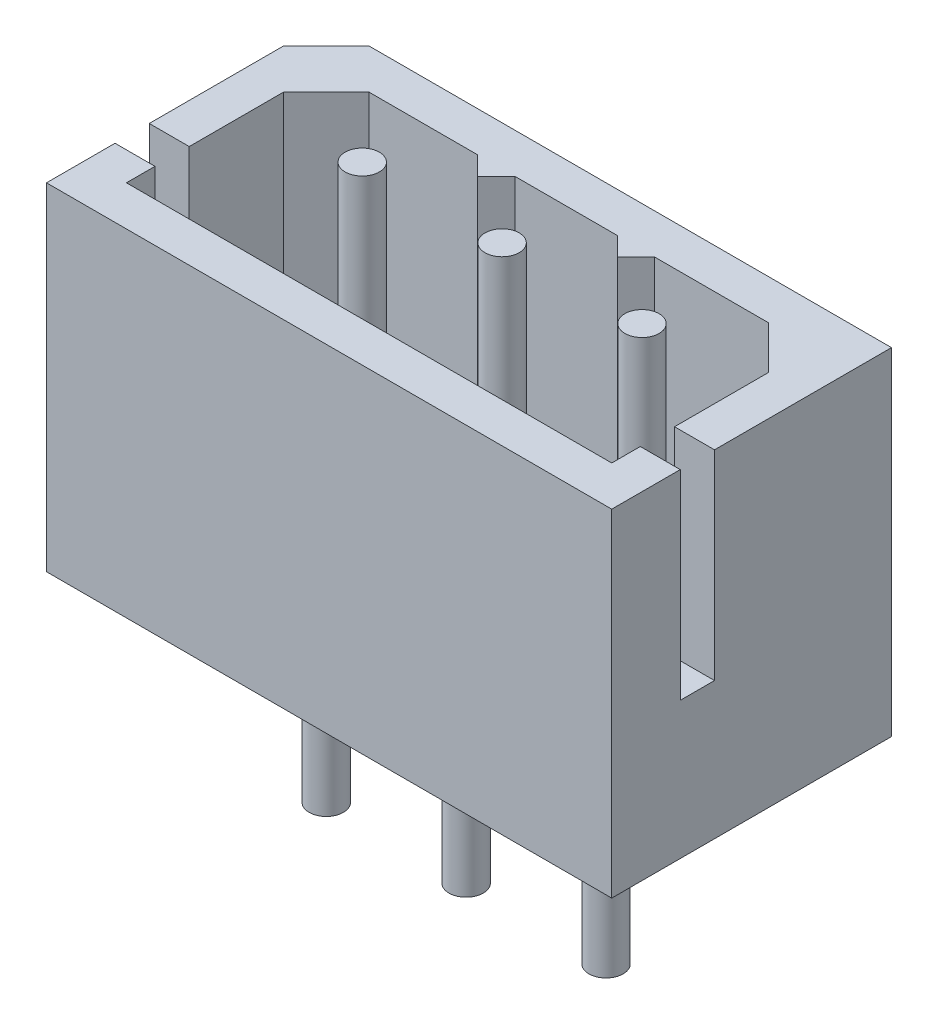
SolidWorks part; units mm, degrees
ref_plane "Front Plane" through (0, 0, 0) normal (0, 0, 1) x (1, 0, 0)
ref_plane "Top Plane" through (0, 0, 0) normal (0, 1, 0) x (1, 0, 0)
ref_plane "Right Plane" through (0, 0, 0) normal (1, 0, 0) x (0, 0, -1)
sketch "Sketch1" plane through (0, 0, 0) normal (0, 1, 0) x (1, 0, 0)
  line L0 (-4.2, 2.45) -> (-4.95, 1.7)
  line L1 (-4.2, 2.45) -> (4.95, 2.45)
  line L2 (-4.95, 1.7) -> (-4.95, -2.45)
  line L3 (-4.95, -2.45) -> (4.95, -2.45)
  line L4 (4.95, 2.45) -> (4.95, -2.45)
  line L5 (-4.95, 2.45) -> (4.95, -2.45) construction
  line L6 (-4.95, -2.45) -> (4.95, 2.45) construction
  point P0 (0, 0)
  dimension "D1" = 4.9
  dimension "D2" = 9.9
extrude "Boss-Extrude1" add sketch "Sketch1" against normal blind 5.9
sketch "Sketch2" plane through (0, -5.9, 0) normal (0, -1, 0) x (1, 0, 0)
  line L0 (-4.95, 0) -> (4.95, 0) construction
  line L1 (-4.95, -1.7) -> (-4.95, 2.45) construction
  line L2 (4.95, 2.45) -> (4.95, -2.45) construction
  line L3 (0, 2.45) -> (0, -2.45) construction
  line L4 (-4.95, 2.45) -> (4.95, 2.45) construction
  line L5 (4.95, -2.45) -> (-4.2, -2.45) construction
  line L6 (-2.5, 0) -> (-0.05, 0) construction
  line L7 (-4.95, -1.7) -> (-4.95, 2.45) construction
  line L8 (4.95, -2.45) -> (-4.2, -2.45) construction
  circle A0 centre (-2.5, 0) radius 0.3
  circle A1 centre (-0.05, 0) radius 0.3
  circle A2 centre (2.4, 0) radius 0.3
  dimension "D1" = 0.6
  dimension "D2" = 2.45
  dimension "D5" = 2.45
  dimension "D4" = 2.45
  dimension "D3" = 3
extrude "Boss-Extrude2" add sketch "Sketch2" along normal blind 3.5
sketch "Sketch3" plane through (0, 0, 0) normal (0, 1, 0) x (1, 0, 0)
  line L0 (-4.95, -2.45) -> (4.95, -2.45) construction
  line L1 (-3.5, 1.75) -> (3.5, 1.75)
  line L2 (-4.25, 1) -> (-4.25, -0.65)
  line L3 (-4.25, -1.75) -> (4.25, -1.75)
  line L4 (4.25, 1) -> (4.25, -0.65)
  line L5 (-4.25, 1.75) -> (4.25, -1.75) construction
  line L6 (-4.25, -1.75) -> (4.25, 1.75) construction
  line L7 (-4.25, 0.63) -> (4.25, 0.63) construction
  line L8 (-2.5, 0.63) -> (-0.05, 0.63) construction
  line L9 (-1.275, 1.75) -> (-1.275, -1.75) construction
  line L10 (-1.275, 1.4218) -> (-1.6032, 1.75)
  line L11 (-1.275, 1.4218) -> (-0.9468, 1.75)
  line L12 (1.175, 1.4218) -> (0.8468, 1.75)
  line L13 (1.175, 1.4218) -> (1.5032, 1.75)
  line L14 (-1.275, 1.4218) -> (1.175, 1.4218) construction
  line L17 (4.95, -0.65) -> (4.25, -0.65)
  line L18 (-3.5, 1.75) -> (-4.25, 1)
  line L19 (3.5, 1.75) -> (4.25, 1)
  line L20 (-4.25, -1.25) -> (-4.95, -1.25)
  line L21 (-4.95, 1.7) -> (-4.95, -2.45) construction
  line L22 (-4.95, -1.25) -> (-4.95, -0.65)
  line L23 (-4.95, -0.65) -> (-4.25, -0.65)
  line L24 (-4.25, -1.25) -> (-4.25, -1.75)
  line L25 (0, -1.75) -> (0, 1.75) construction
  line L26 (4.95, -1.25) -> (4.95, -0.65)
  line L27 (4.25, -1.25) -> (4.95, -1.25)
  line L28 (4.25, -1.25) -> (4.25, -1.75)
  circle A0 centre (-2.5, 0.63) radius 0.3
  circle A1 centre (-0.05, 0.63) radius 0.3
  circle A2 centre (2.4, 0.63) radius 0.3
  point P0 (0, 0)
  line M11 (4.95, -2.45) -> (4.95, 2.45)
  line M14 (-4.95, 1.7) -> (-4.95, -2.45)
  dimension "D4" = 1.75
  dimension "D5" = 0.6
  dimension "D8" = 2.975
  dimension "D1" = 8.5
  dimension "D2" = 0.7
  dimension "D3" = 2.38
  dimension "D7" = 2.45
  dimension "D9" = 45
  dimension "D10" = 45
  dimension "D11" = 0.6565
  dimension "D13" = 2.45
  dimension "D14" = 0.6
  dimension "D15" = 0.5
  dimension "D6" = 3
  dimension "D12" = 2
extrude "Cut-Extrude1" cut sketch "Sketch3" against normal blind 3.5 contours L28 L27 L17 L4 L19 L1 L11 L10 L18 L2 L23 L20 L24 L3 A2 A1 A0 M11 M14 region at (0.0018, 0, 0.0873)
